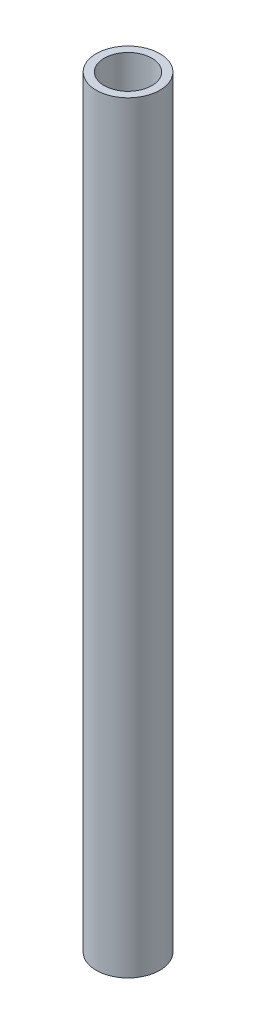
SolidWorks part; units mm, degrees
ref_plane "Front Plane" through (0, 0, 0) normal (0, 0, 1) x (1, 0, 0)
ref_plane "Top Plane" through (0, 0, 0) normal (0, 1, 0) x (1, 0, 0)
ref_plane "Right Plane" through (0, 0, 0) normal (1, 0, 0) x (0, 0, -1)
sketch "Sketch2" plane through (0, 0, 0) normal (0, 1, 0) x (1, 0, 0)
  circle A0 centre (0, 0) radius 19.05
  circle A1 centre (0, 0) radius 25.4
  dimension "PipeDiameter" = 50.8
  dimension "PipeWallThickness " = 6.35
extrude "Boss-Extrude1" add sketch "Sketch2" along normal blind 609.6
equation "\"Pstrut_L\"= 24in'Primary Strut Length"
equation "\"Pstrut_T\"= 0.25in'Primary Strut Thickness"
equation "\"Pstrut_D\"= 2in'Primary Strut Diameter "
equation "\"Sstrut_T\" = 0.25in'Secondary Strut Thickness"
equation "\"Sstrut_L\"= 24in'Secondary Strut Length"
equation "\"Sstrut_D\"= 2in'Secondary Strut Diameter"
equation "\"LegStance\"= 7in"
equation "\"PipeDiameter@Sketch2\"=\"Pstrut_D\""
equation "\"PipeWallThickness @Sketch2\" = \"Pstrut_T\""
equation "\"D1@Boss-Extrude1\"=\"Pstrut_L\""
